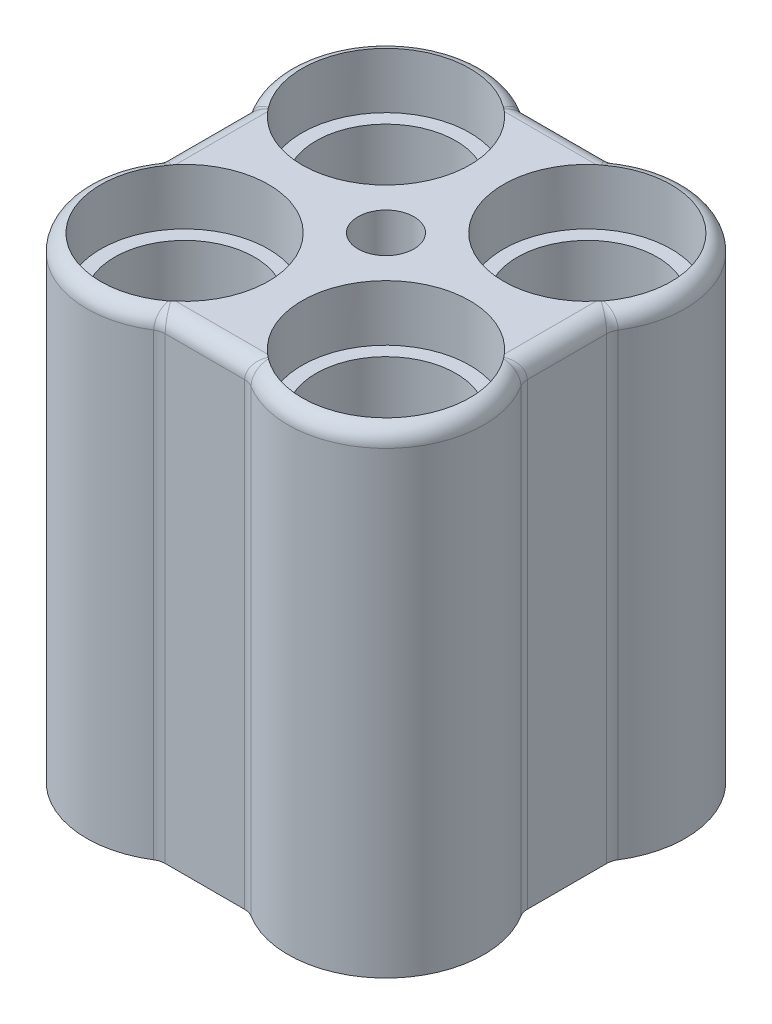
SolidWorks part; units mm, degrees
ref_plane "Front Plane" through (0, 0, 0) normal (0, 0, 1) x (1, 0, 0)
ref_plane "Top Plane" through (0, 0, 0) normal (0, 1, 0) x (1, 0, 0)
ref_plane "Right Plane" through (0, 0, 0) normal (1, 0, 0) x (0, 0, -1)
sketch "Sketch2" plane through (0, 0, 0) normal (0, 1, 0) x (1, 0, 0)
  line L0 (0, 32.5948) -> (0, -36.7496) construction
  line L1 (-39.8171, 0) -> (53.186, 0) construction
  line L2 (0, 32.3614) -> (0, -32.3614)
  line L3 (32.3614, 0) -> (-32.3614, 0)
  line L4 (-32.3614, -8) -> (-32.3614, 8)
  line L5 (-8, 32.3614) -> (8, 32.3614)
  line L6 (32.3614, -8) -> (32.3614, 8)
  line L7 (-8, -32.3614) -> (8, -32.3614)
  arc A0 (-8, 32.3614) -> (-32.3614, 8) centre (-18, 18) ccw
  arc A3 (8, 32.3614) -> (32.3614, 8) centre (18, 18) cw
  arc A4 (8, -32.3614) -> (32.3614, -8) centre (18, -18) ccw
  arc A7 (-8, -32.3614) -> (-32.3614, -8) centre (-18, -18) cw
  point P13 (0, 0)
  point P29 (0, 0)
  dimension "D1" = 35
  dimension "D2" = 8
  dimension "D3" = 8
  dimension "D4" = 18
  dimension "D5" = 18
extrude "Boss-Extrude1" add sketch "Sketch2" against normal blind 85 contours A0 L4 A7 L7 A4 L6 A3 L5
sketch "Sketch7" plane through (0, 0, 0) normal (0, 1, 0) x (1, 0, 0)
  point P0 (-18, 18)
  point P4 (18, 18)
  point P7 (18, -18)
  point P10 (-18, -18)
hole_wizard "Hole1" positions "Sketch7" profile "Sketch6" legacy
sketch "Sketch6" plane through (-18, 0, -18) normal (1, 0, 0) x (0, 0, 1)
  line L0 (0, 0) -> (0, 80)
  line L1 (0, 80) -> (12.5, 80)
  line L2 (12.5, 80) -> (12.5, 10)
  line L3 (12.5, 10) -> (15, 10)
  line L4 (15, 10) -> (15, 0)
  line L5 (15, 0) -> (0, 0)
  line L6 (0, 110) -> (0, -10) construction
  dimension "Diameter" = 25
  dimension "Depth" = 80
  dimension "C-Bore Diameter" = 30
  dimension "C-Bore Depth" = 10
sketch "Sketch8" plane through (0, 0, 0) normal (0, 1, 0) x (1, 0, 0)
  line L0 (0, 32.5092) -> (0, -35.747) construction
  line L1 (-35.3532, 0) -> (38.241, 0) construction
  point P7 (18, 18)
  point P10 (18, -18)
  point P13 (-18, -18)
sketch "Sketch17" plane through (0, 0, 0) normal (0, 1, 0) x (1, 0, 0)
  point P0 (0, 0)
hole_wizard "Hole3" positions "Sketch17" profile "Sketch16" legacy end condition through all
sketch "Sketch16" plane through (0, 0, 0) normal (1, 0, 0) x (0, 0, 1)
  line L0 (0, 0) -> (0, 85)
  line L1 (0, 85) -> (5, 85)
  line L2 (5, 85) -> (5, 0)
  line L3 (5, 0) -> (0, 0)
  line L4 (0, 110) -> (0, -10) construction
  dimension "Diameter" = 10
  dimension "Depth" = 85
fillet "Fillet1" radius 10 1 edges at (-18, -80, -5.5)
fillet "Fillet2" radius 10 3 edges at (18, -80, 30.5) (-18, -80, 30.5) (18, -80, -5.5)
fillet "Fillet3" radius 3 8 edges at (30.3744, 0, -30.3744) (32.3614, 0, 0) (30.3744, 0, 30.3744) (0, 0, 32.3614) (-30.3744, 0, 30.3744) (-32.3614, 0, 0) (-30.3744, 0, -30.3744) (0, 0, -32.3614)
fillet "Fillet4" radius 3 16 edges at (-8.3312, -0.7306, -31.3235) (8.1921, -1.1919, -31.7553) (31.3235, -0.7306, -8.3312) (31.3235, -0.7306, 8.3312) (8.3312, -0.7306, 31.3235) (-8.3312, -0.7306, 31.3235) (-31.3235, -0.7306, 8.3312) (-31.3235, -0.7306, -8.3312) (-8, -44, -32.3614) (8, -44, -32.3614) (32.3614, -44, -8) (32.3614, -44, 8) (8, -44, 32.3614) (-8, -44, 32.3614) (-32.3614, -44, 8) (-32.3614, -44, -8)
